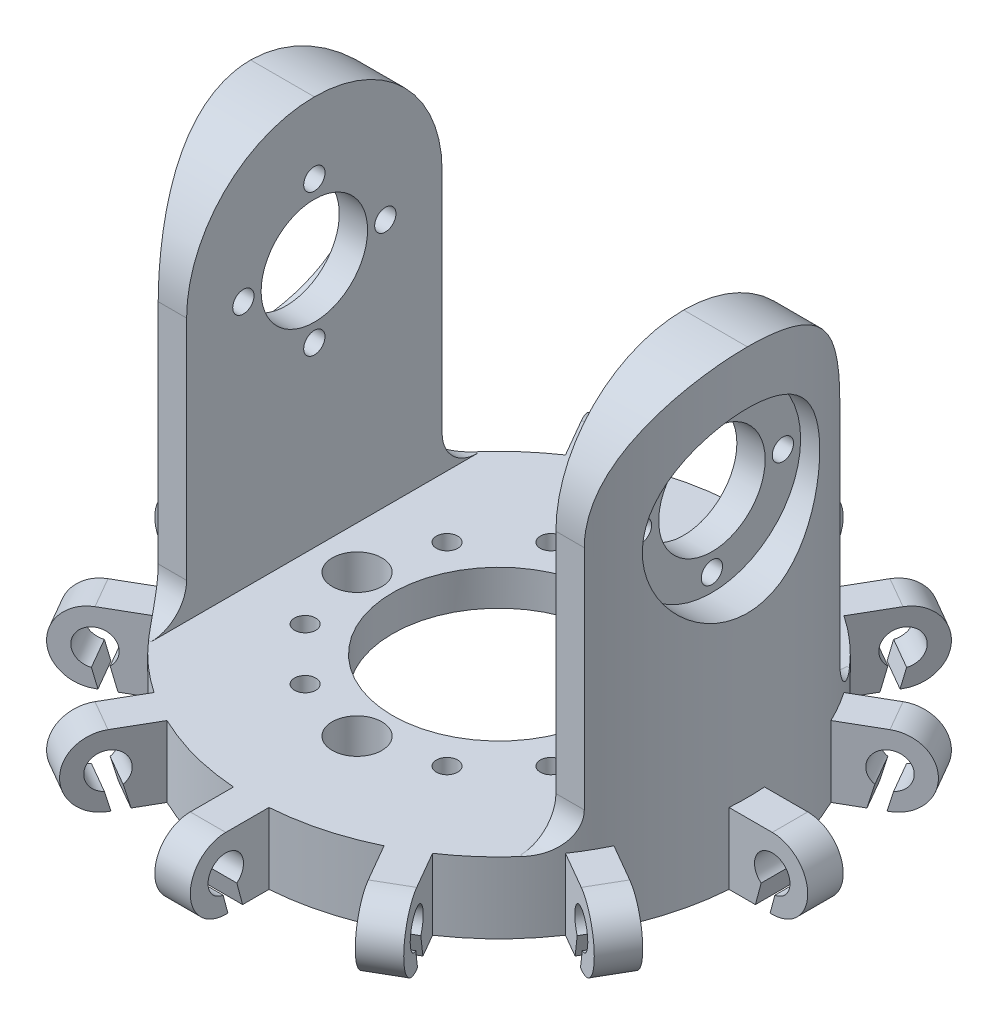
SolidWorks part; units mm, degrees
ref_plane "前视基准面" through (0, 0, 0) normal (0, 0, 1) x (1, 0, 0)
ref_plane "上视基准面" through (0, 0, 0) normal (0, 1, 0) x (1, 0, 0)
ref_plane "右视基准面" through (0, 0, 0) normal (1, 0, 0) x (0, 0, -1)
other "Configuration Table"
sketch "Sketch4" plane through (0, 0, 0) normal (0, 1, 0) x (1, 0, 0)
  circle A0 centre (0, 0) radius 17.5
  dimension "D1" = 35
extrude "Boss-Extrude2" add sketch "Sketch4" along normal blind 5
sketch "Sketch5" plane through (0, 5, 0) normal (0, 1, 0) x (1, 0, 0)
  line L0 (0, 0) -> (0, 4.951) construction
  line L1 (0, 0) -> (17.5, 0) construction
  line L2 (13.0083, 11.7061) -> (13.0083, -11.7061)
  line L3 (-13.0083, 11.7061) -> (-13.0083, -11.7061)
  line L4 (13.0083, 9) -> (15.0083, 9)
  line L5 (13.0083, -9) -> (15.0083, -9)
  line L6 (-13.0083, 9) -> (-15.0083, 9)
  line L7 (-13.0083, -9) -> (-15.0083, -9)
  circle A0 centre (0, 0) radius 17.5
  circle A1 centre (0, 0) radius 17.5 construction
  point P13 (13.0083, 0)
  circle M3 centre (0, 0) radius 17.5
  dimension "D1" = 18
  dimension "D2" = 2
extrude "Boss-Extrude3" add sketch "Sketch5" along normal blind 27.5 contours L7 L3 L6 M3 | L2 L5 L4 M3 region at (14.9246, 5, 0) region at (-14.9246, 5, 0)
fillet "Fillet1" radius 9 4 edges at (-14.0083, 32.5, -9) (-14.0083, 32.5, 9) (14.0083, 32.5, -9) (14.0083, 32.5, 9)
sketch "Sketch6" plane through (0, 5, 0) normal (0, 1, 0) x (1, 0, 0)
  circle A0 centre (0, 0) radius 7.5
  dimension "D1" = 15
extrude "Cut-Extrude3" cut sketch "Sketch6" against normal blind 15
sketch "Sketch7" plane through (0, 0, 0) normal (0, -1, 0) x (1, 0, 0)
  circle A0 centre (0, 0) radius 12.5
  dimension "D1" = 25
extrude "Cut-Extrude4" cut sketch "Sketch7" against normal blind 2.5
sketch "Sketch8" plane through (0, 2.5, 0) normal (0, -1, 0) x (1, 0, 0)
  line L0 (0, 10) -> (0, 0) construction
  circle A0 centre (0, 0) radius 10 construction
  circle A1 centre (0, 10) radius 0.75
  circle A2 centre (0, 0) radius 10 construction
  circle A3 centre (5, 8.6603) radius 0.75
  circle A4 centre (0, 0) radius 10 construction
  circle A5 centre (8.6603, 5) radius 0.75
  circle A6 centre (0, 0) radius 10 construction
  circle A7 centre (10, 0) radius 0.75
  circle A8 centre (0, 0) radius 10 construction
  circle A9 centre (8.6603, -5) radius 0.75
  circle A10 centre (0, 0) radius 10 construction
  circle A11 centre (5, -8.6603) radius 0.75
  circle A12 centre (0, 0) radius 10 construction
  circle A13 centre (0, -10) radius 0.75
  circle A14 centre (0, 0) radius 10 construction
  circle A15 centre (-5, -8.6603) radius 0.75
  circle A16 centre (0, 0) radius 10 construction
  circle A17 centre (-8.6603, -5) radius 0.75
  circle A18 centre (0, 0) radius 10 construction
  circle A19 centre (-10, 0) radius 0.75
  circle A20 centre (0, 0) radius 10 construction
  circle A21 centre (-8.6603, 5) radius 0.75
  circle A22 centre (0, 0) radius 10 construction
  circle A23 centre (-5, 8.6603) radius 0.75
  point P22 (0, 0)
  dimension "D1" = 20
  dimension "D2" = 1.5
  dimension "D3" = 12
extrude "Cut-Extrude5" cut sketch "Sketch8" against normal blind 2.5
sketch "Sketch9" plane through (13.0083, 0, 0) normal (-1, 0, 0) x (0, 0, 1)
  line L0 (-9, 5) -> (9, 5) construction
  line L1 (9, 5) -> (0, 5) construction
  line L2 (0, 22.5) -> (0, 32.5) construction
  circle A0 centre (0, 22.5) radius 3.75
  point P7 (0, 30)
  point P8 (0, 30)
  point P12 (0, 0)
  point P14 (0, 0)
  point P15 (0, 30)
  point P16 (0, 0)
  point P17 (0, 29.788)
  point P18 (0, 0)
  dimension "D1" = 7.5
  dimension "D2" = 10
extrude "Cut-Extrude6" cut sketch "Sketch9" against normal through all both and the other way through all
ref_plane "Plane1" through (17.5, 0, 0) normal (1, 0, 0) x (0, 0, -1)
sketch "Sketch10" plane through (17.5, 0, 0) normal (1, 0, 0) x (0, 0, -1)
  circle A0 centre (0, 22.5) radius 6.25
  dimension "D1" = 12.5
extrude "Cut-Extrude7" cut sketch "Sketch10" against normal blind 2.5
mirror "Mirror1" about plane through (0, 0, 0) normal (1, 0, 0) of "Cut-Extrude7"
fillet "Fillet2" radius 2.5 4 edges at (-14.0083, 5, -9) (14.0083, 5, -9) (14.0083, 5, 9) (-14.0083, 5, 9)
sketch "Sketch11" plane through (0, 0, 0) normal (1, 0, 0) x (0, 0, -1)
  line L0 (-17.5, 5) -> (-17.5, 0)
  line L1 (-17.5, 2.5) -> (-20.5, 2.5) construction
  line L2 (-20.5, 5) -> (-17.5, 5)
  line L3 (-20.5, 0) -> (-17.5, 0)
  line L4 (-17.5, 5) -> (-16.5, 5)
  line L5 (-16.5, 5) -> (-16.5, 0)
  line L6 (-16.5, 0) -> (-17.5, 0)
  circle A0 centre (-20.5, 2.5) radius 2.5
  circle A1 centre (-20.5, 2.5) radius 1.25
  dimension "D2" = 5
  dimension "D3" = 2.5
  dimension "D1" = 3
  dimension "D4" = 1
extrude "Boss-Extrude4" add sketch "Sketch11" along normal mid plane 2.5 contours A0 A1 | L1 L0 L2 A0 | L0 L1 A0 L3 | L6 L5 L4 L0 region at (0, 2.5, 17) region at (0, 4.108, 18.1684) region at (0, 0.892, 18.1684) region at (0, 4.2178, 18.7822)
sketch "Sketch12" plane through (1.25, 0, 0) normal (1, 0, 0) x (0, 0, -1)
  line L0 (-20.5, 2.5) -> (-19.8301, 0) construction
  line L1 (-20.5, 0) -> (-17.4553, 0) construction
  line L2 (-20.5, 2.5) -> (-19.25, 2.5) construction
  line L3 (-20.5, 2.5) -> (-20.017, 2.6294)
  line L4 (-20.017, 2.6294) -> (-19.3125, 0)
  line L5 (-19.3125, 0) -> (-19.8301, 0)
  line L6 (-19.8301, 0) -> (-20.3478, 0)
  line L7 (-20.3478, 0) -> (-20.983, 2.3706)
  line L8 (-20.983, 2.3706) -> (-20.5, 2.5)
  circle A0 centre (-20.5, 2.5) radius 1.25 construction
  dimension "D1" = 75
  dimension "D2" = 0.5
extrude "Cut-Extrude8" cut sketch "Sketch12" against normal blind 2.5
pattern_circular "CirPattern2" count 12 over 360 about axis through (0, 5, 0) along (0, 1, 0) of "Boss-Extrude4", "Cut-Extrude8"
sketch "Sketch14" plane through (0, 2.5, 0) normal (0, -1, 0) x (1, 0, 0)
  circle A0 centre (0, 10) radius 1.75
  circle A1 centre (10, 0) radius 1.75
  circle A2 centre (0, -10) radius 1.75
  circle A3 centre (-10, 0) radius 1.75
  point P12 (0, 0)
  dimension "D1" = 3.5
  dimension "D2" = 4
extrude "Cut-Extrude9" cut sketch "Sketch14" against normal blind 10
sketch "Sketch15" plane through (-15, 0, 0) normal (-1, 0, 0) x (0, 0, 1)
  circle A0 centre (0, 22.5) radius 5 construction
  circle A1 centre (0, 27.5) radius 0.75
  point P14 (1.25, 23.75)
  dimension "D1" = 10
  dimension "D2" = 1.5
extrude "Cut-Extrude10" cut sketch "Sketch15" against normal through all
pattern_circular "CirPattern3" count 4 over 360 about axis through (-15, 22.5, 0) along (1, 0, 0) of "Cut-Extrude10"
sketch "Sketch16" plane through (0, 0, 0) normal (0, -1, 0) x (1, 0, 0)
  circle A0 centre (0, 0) radius 15 construction
  circle A1 centre (0, 15) radius 1.25
  circle A2 centre (0, 0) radius 15 construction
  circle A3 centre (12.9904, 7.5) radius 1.25
  circle A4 centre (0, 0) radius 15 construction
  circle A5 centre (12.9904, -7.5) radius 1.25
  circle A6 centre (0, 0) radius 15 construction
  circle A7 centre (0, -15) radius 1.25
  circle A8 centre (0, 0) radius 15 construction
  circle A9 centre (-12.9904, -7.5) radius 1.25
  circle A10 centre (0, 0) radius 15 construction
  circle A11 centre (-12.9904, 7.5) radius 1.25
  point P17 (0, 0)
  dimension "D1" = 30
  dimension "D2" = 2.5
  dimension "D3" = 6
extrude "Cut-Extrude11" cut sketch "Sketch16" against normal blind 2.5
